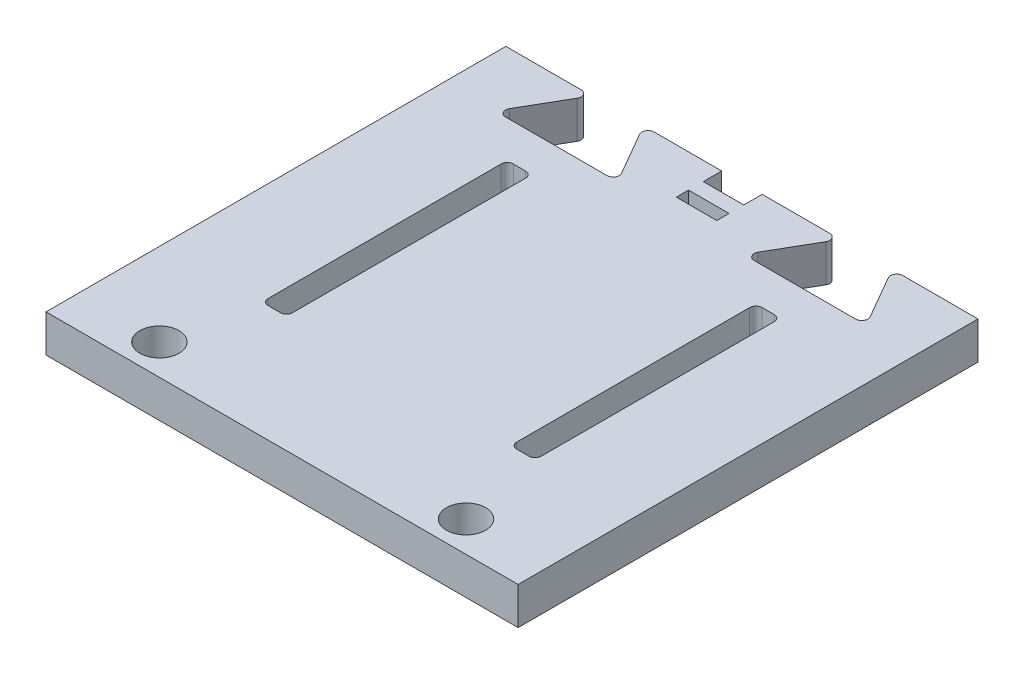
SolidWorks part; units mm, degrees
ref_plane "Front Plane" through (0, 0, 0) normal (0, 0, 1) x (1, 0, 0)
ref_plane "Top Plane" through (0, 0, 0) normal (0, 1, 0) x (1, 0, 0)
ref_plane "Right Plane" through (0, 0, 0) normal (1, 0, 0) x (0, 0, -1)
sketch "Sketch1" plane through (0, 0, 0) normal (0, 1, 0) x (1, 0, 0)
  line L0 (-19.25, 0) -> (-19.25, 37.5)
  line L1 (-19.25, 37.5) -> (-12.25, 37.5)
  line L2 (-12.25, 37.5) -> (-15.1368, 32.5)
  line L3 (-15.1368, 32.5) -> (-5.1368, 32.5)
  line L4 (-5.1368, 32.5) -> (-8.0235, 37.5)
  line L5 (-8.0235, 37.5) -> (8.0235, 37.5)
  line L6 (8.0235, 37.5) -> (5.1368, 32.5)
  line L7 (5.1368, 32.5) -> (15.1368, 32.5)
  line L8 (15.1368, 32.5) -> (12.25, 37.5)
  line L9 (12.25, 37.5) -> (19.25, 37.5)
  line L10 (19.25, 37.5) -> (19.25, 0)
  line L11 (19.25, 0) -> (-19.25, 0)
  point P3 (0, 0)
  dimension "D1" = 37.5
  dimension "D2" = 38.5
  dimension "D3" = 7
  dimension "D4" = 10
  dimension "D5" = 10
  dimension "D6" = 7
  dimension "D7" = 5
  dimension "D11" = 60
  dimension "D12" = 60
  dimension "D13" = 60
extrude "Boss-Extrude1" add sketch "Sketch1" along normal blind 3.05
fillet "Fillet3" radius 0.5 8 edges at (15.1368, 1.525, -32.5) (12.25, 1.525, -37.5) (5.1368, 1.525, -32.5) (8.0235, 1.525, -37.5) (-8.0235, 1.525, -37.5) (-5.1368, 1.525, -32.5) (-15.1368, 1.525, -32.5) (-12.25, 1.525, -37.5)
sketch "Sketch2" plane through (0, 3.05, 0) normal (0, 1, 0) x (1, 0, 0)
  line L0 (0, 0) -> (0, 32.5) construction
  line L3 (1.65, 36) -> (-1.65, 36)
  line L4 (1.65, 36) -> (1.65, 76)
  line L5 (1.65, 76) -> (-1.65, 76)
  line L6 (-1.65, 36) -> (-1.65, 76)
  line L7 (-1.65, 34.8) -> (1.65, 34.8)
  line L8 (-1.65, 34.8) -> (-1.65, 33.8)
  line L9 (-1.65, 33.8) -> (1.65, 33.8)
  line L10 (1.65, 34.8) -> (1.65, 33.8)
  line L11 (-19.25, 0) -> (19.25, 0) construction
  line L12 (-19.25, 0) -> (-19.25, 82.5) construction
  line L13 (-19.25, 82.5) -> (19.25, 82.5) construction
  line L14 (19.25, 0) -> (19.25, 82.5) construction
  point P8 (0, 36)
  point P13 (0, 34.8)
  dimension "D1" = 3.3
  dimension "D2" = 40
  dimension "D3" = 1
  dimension "D4" = 1.2
  dimension "D5" = 82.5
  dimension "D6" = 6.5
extrude "Cut-Extrude1" cut sketch "Sketch2" against normal through all
sketch "Sketch6" plane through (0, 3.05, 0) normal (0, 1, 0) x (1, 0, 0)
  line L0 (0, 0) -> (0, 18.0616) construction
  line L1 (-6.0028, 32.5) -> (-14.2707, 32.5) construction
  line L2 (-11.1368, 29.5) -> (-9.1368, 29.5)
  line L3 (-11.1368, 29.5) -> (-11.1368, 9.5)
  line L4 (-11.1368, 9.5) -> (-9.1368, 9.5)
  line L5 (-9.1368, 29.5) -> (-9.1368, 9.5)
  line L7 (11.1368, 9.5) -> (9.1368, 9.5)
  line L8 (9.1368, 29.5) -> (9.1368, 9.5)
  line L9 (11.1368, 29.5) -> (9.1368, 29.5)
  line L10 (11.1368, 29.5) -> (11.1368, 9.5)
  line L11 (-19.25, 0) -> (19.25, 0) construction
  point P9 (-10.1368, 32.5)
  point P10 (-10.1368, 29.5)
  dimension "D1" = 2
  dimension "D2" = 3
  dimension "D3" = 9.5
extrude "Cut-Extrude2" cut sketch "Sketch6" against normal through all
fillet "Fillet4" radius 0.5 8 edges at (9.1368, 1.525, -9.5) (11.1368, 1.525, -9.5) (11.1368, 1.525, -29.5) (9.1368, 1.525, -29.5) (-11.1368, 1.525, -9.5) (-9.1368, 1.525, -9.5) (-9.1368, 1.525, -29.5) (-11.1368, 1.525, -29.5)
sketch "Head Mounting Hole Locations" plane through (0, 3.05, 0) normal (0, 1, 0) x (1, 0, 0)
  line L0 (0, 0) -> (0, 16.3288) construction
  line L1 (-19.25, 0) -> (19.25, 0) construction
  circle A0 centre (-12.5, 2.5) radius 1.5
  circle A1 centre (12.5, 2.5) radius 1.5
  dimension "D1" = 3
  dimension "D2" = 12.5
  dimension "D3" = 2.5
hole_wizard "M3 Clearance Head Mounting Holes" positions "Sketch4" profile "Sketch5" hole size "M3" standard "ANSI Metric" end condition through all
sketch "Sketch4" plane through (0, 3.05, 0) normal (0, 1, 0) x (1, 0, 0)
  point P0 (-12.5, 2.5)
  point P3 (12.5, 2.5)
sketch "Sketch5" plane through (-12.5, 3.05, -2.5) normal (1, 0, 0) x (0, 0, 1)
  line L0 (0, 0) -> (0, 3.05)
  line L1 (0, 3.05) -> (1.6, 3.05)
  line L2 (1.6, 3.05) -> (1.6, 0)
  line L5 (1.6, 0) -> (0, 0)
  line L11 (0, -6.35) -> (0, 107.95) construction
  dimension "Thru Hole Dia." = 3.2
  dimension "Thru Hole Depth" = 3.05
